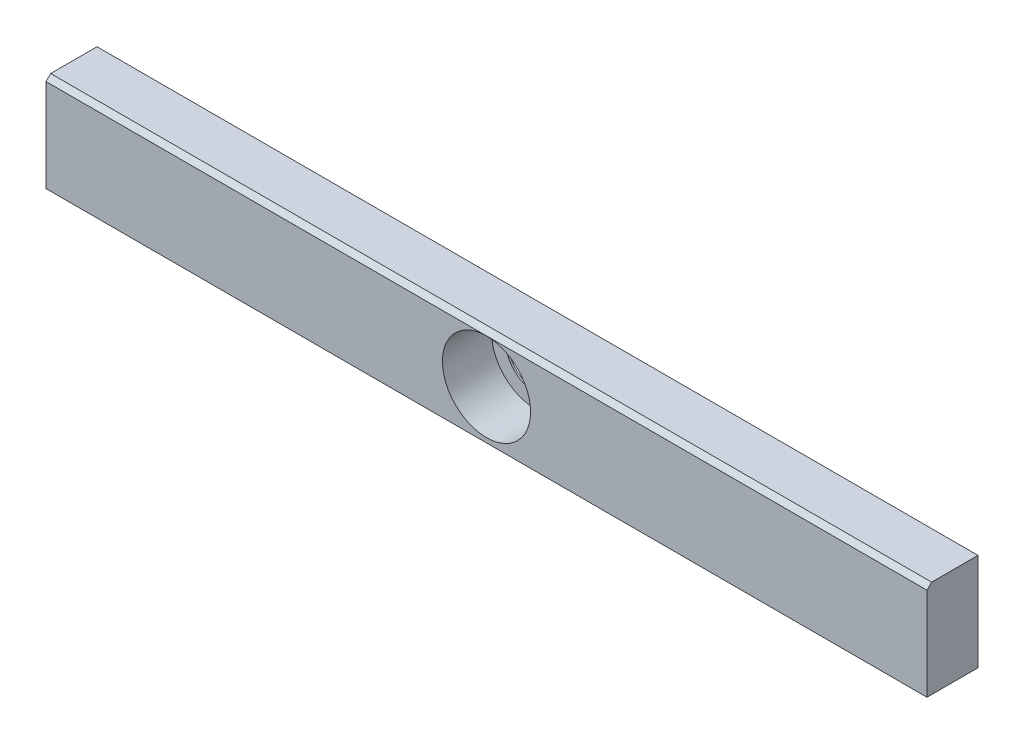
SolidWorks part; units mm, degrees
ref_plane "Front Plane" through (0, 0, 0) normal (0, 0, 1) x (1, 0, 0)
ref_plane "Top Plane" through (0, 0, 0) normal (0, 1, 0) x (1, 0, 0)
ref_plane "Right Plane" through (0, 0, 0) normal (1, 0, 0) x (0, 0, -1)
sketch "Sketch1" plane through (0, 0, 0) normal (0, 0, 1) x (1, 0, 0)
  line L1 (-475, 52.5) -> (475, 52.5)
  line L2 (-475, 52.5) -> (-475, -52.5)
  line L3 (-475, -52.5) -> (475, -52.5)
  line L4 (475, 52.5) -> (475, -52.5)
  line L5 (-475, 52.5) -> (475, -52.5) construction
  line L6 (-475, -52.5) -> (475, 52.5) construction
  point P0 (0, 0)
  dimension "D1" = 950
  dimension "D2" = 105
extrude "Boss-Extrude1" add sketch "Sketch1" along normal mid plane 55
sketch "Sketch2" plane through (0, 0, 27.5) normal (0, 0, 1) x (1, 0, 0)
  circle A0 centre (0, 0) radius 47.5
  dimension "D1" = 95
extrude "Cut-Extrude1" cut sketch "Sketch2" against normal blind 53
sketch "Sketch3" plane through (0, 0, -25.5) normal (0, 0, 1) x (1, 0, 0)
  circle A0 centre (0, 0) radius 32.5
  dimension "D1" = 65
extrude "Cut-Extrude2" cut sketch "Sketch3" against normal through all
chamfer "Chamfer1" distance 5 angle 45 1 edges at (0, 52.5, 27.5)
